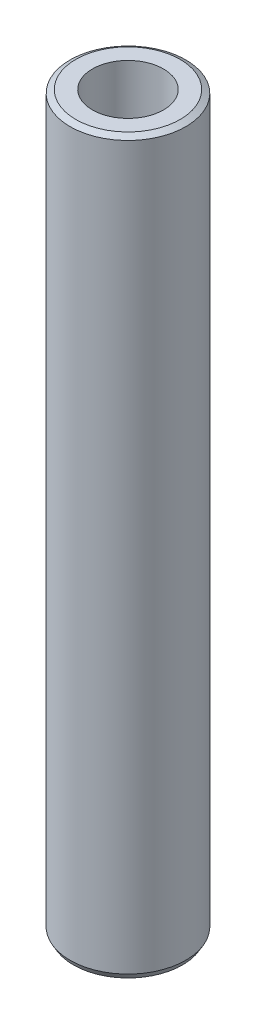
SolidWorks part; units mm, degrees
ref_plane "Front Plane" through (0, 0, 0) normal (0, 0, 1) x (1, 0, 0)
ref_plane "Top Plane" through (0, 0, 0) normal (0, 1, 0) x (1, 0, 0)
ref_plane "Right Plane" through (0, 0, 0) normal (1, 0, 0) x (0, 0, -1)
sketch "Sketch1" plane through (0, 0, 0) normal (0, 1, 0) x (1, 0, 0)
  circle A0 centre (0, 0) radius 47.5
  dimension "SHAFT_OD" = 95
extrude "Boss-Extrude1" add sketch "Sketch1" along normal blind 600
sketch "Sketch2" plane through (0, 0, 0) normal (0, 1, 0) x (1, 0, 0)
  circle A0 centre (0, 0) radius 29.1758
  dimension "BORE_D" = 58.3516
extrude "Cut-Extrude1" cut sketch "Sketch2" along normal through all
chamfer "Chamfer1" distance 2.7163 angle 60 2 edges at (0, 600, 47.5) (0, 0, 47.5) first distance on face at (0, 600, 47.5) first distance on face at (0, 0, 29.1758)
